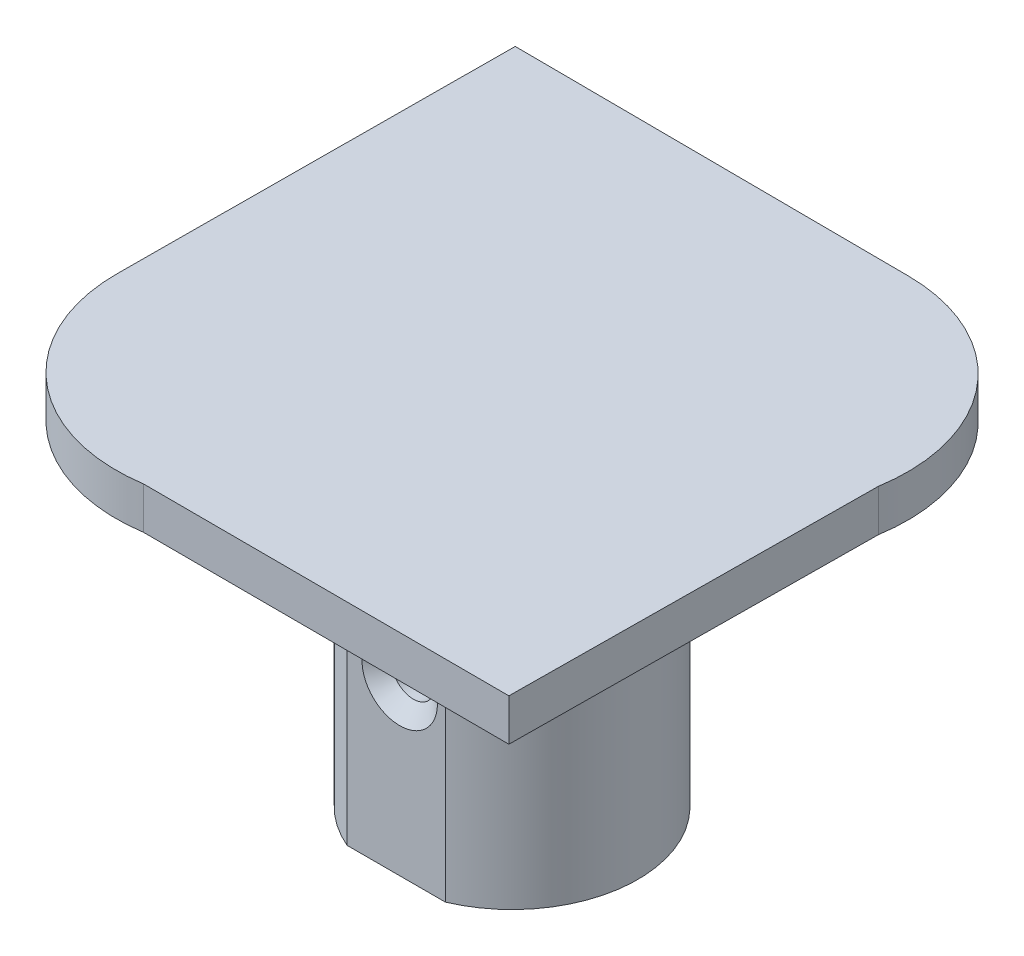
SolidWorks part; units mm, degrees
material "ABS"
ref_plane "Front Plane" through (0, 0, 0) normal (0, 0, 1) x (1, 0, 0)
ref_plane "Top Plane" through (0, 0, 0) normal (0, 1, 0) x (1, 0, 0)
ref_plane "Right Plane" through (0, 0, 0) normal (1, 0, 0) x (0, 0, -1)
sketch "Sketch2" plane through (0, 0, 0) normal (0, 1, 0) x (1, 0, 0)
  line L0 (2.8358, -0.2904) -> (10.2697, -0.2904)
  line L1 (2.8358, 17.2492) -> (10.2697, 17.2492)
  line L2 (6.5528, -0.2904) -> (6.5528, 17.2492) construction
  arc A0 (2.8358, 17.2492) -> (2.8358, -0.2904) centre (6.5528, 8.4794) ccw
  circle A1 centre (6.5528, 8.4794) radius 6.35
  arc A2 (10.2697, -0.2904) -> (10.2697, 17.2492) centre (6.5528, 8.4794) ccw
  dimension "D1" = 12.7
  dimension "D2" = 3.175
sketch "Sketch3" plane through (0, 0, 0) normal (0, 1, 0) x (1, 0, 0)
  line L0 (0, -12.8694) -> (27.7233, -12.933)
  line L1 (-14.7878, -0.0506) -> (-14.6178, 29.8917)
  line L4 (-14.6178, 29.8917) -> (27.7233, -12.933) construction
  line L5 (27.9746, 14.7893) -> (27.7233, -12.933)
  line L6 (15.3245, 29.7217) -> (-14.6178, 29.8917)
  arc A0 (-14.7878, -0.0506) -> (0, -12.8694) centre (-1.9188, -0.1438) ccw
  arc A2 (15.3245, 29.7217) -> (27.9746, 14.7893) centre (15.2716, 16.8524) cw
  point P8 (6.5528, 8.4794)
  dimension "D1" = 12.8694
extrude "Boss-Extrude1" add sketch "Sketch3" along normal blind 3.175 contours L4 L1 A0 L0 | L6 L4 L5 A2 | L0 L5 A2 L6 L1 A0 region at (-0.1371, 0, -1.8095) region at (13.2982, 0, -15.093)
ref_plane "Plane6" through (0, 0, 0) normal (0, -1, 0) x (-1, 0, 0)
sketch "Sketch11" plane through (0, 0, 0) normal (0, 1, 0) x (1, 0, 0)
  line L0 (20.07, -8.458) -> (21.4908, -8.4607)
  spline S0 degree 3 poles (22.9265, -1.3184) (22.9265, -4.6505) (22.9265, -7.9835) (22.9265, -11.3169) knots 3 3 3 3 4 4 4 4
  spline S1 degree 3 poles (12.9265, -1.3184) (16.2589, -1.3184) (19.5927, -1.3184) (22.9265, -1.3184) knots 2 2 2 2 3 3 3 3
  spline S2 degree 3 poles (12.9265, -11.3169) (12.9265, -7.9851) (12.9265, -4.6531) (12.9265, -1.3184) knots 1 1 1 1 2 2 2 2
  spline S3 degree 3 poles (22.9265, -11.3169) (19.5937, -11.3169) (16.2609, -11.3169) (12.9265, -11.3169) knots 0 0 0 0 1 1 1 1
  spline S4 degree 3 poles (15.7816, -4.1748) (17.1943, -4.1744) (20.0443, -4.1757) (20.0617, -4.1773) knots 0 0 0 0 1 1 1 1
  spline S5 degree 3 poles (20.0617, -4.1773) (20.0642, -4.1931) (20.0678, -7.048) (20.0673, -8.4607) knots 1 1 1 1 2 2 2 2
  spline S6 degree 2 poles (20.0673, -8.4607) (18.1734, -8.458) (17.2149, -8.458) knots 2 2 2 3 3 3
  spline S7 degree 3 poles (17.2149, -8.458) (17.2149, -8.9351) (17.2149, -9.4058) (17.2149, -9.8824) knots 3 3 3 3 4 4 4 4
  spline S8 degree 3 poles (17.2149, -9.8824) (16.7341, -9.8824) (16.2635, -9.8824) (15.7859, -9.8824) knots 4 4 4 4 5 5 5 5
  spline S9 degree 2 poles (15.7859, -9.8824) (15.7847, -9.8591) (15.7816, -4.1748) knots 5 5 5 6 6 6
  spline S10 degree 3 poles (15.7843, -4.1721) (15.3121, -4.1721) (14.8399, -4.1721) (14.3608, -4.1721) knots 0 0 0 0 1 1 1 1
  spline S11 degree 3 poles (14.3608, -4.1721) (14.3608, -3.6982) (14.3608, -3.2277) (14.3608, -2.7508) knots 1 1 1 1 2 2 2 2
  spline S12 degree 3 poles (14.3608, -2.7508) (14.8302, -2.7508) (15.3006, -2.7508) (15.7816, -2.7508) knots 2 2 2 2 3 3 3 3
  spline S13 degree 2 poles (15.7816, -2.7508) (15.7816, -3.2259) (15.7843, -4.1721) knots 3 3 3 4 4 4
  spline S15 degree 3 poles (20.07, -9.882) (20.07, -9.4069) (20.07, -8.9325) (20.07, -8.458) knots 2 2 2 2 3 3 3 3
  spline S16 degree 3 poles (21.4908, -9.882) (21.0214, -9.882) (20.551, -9.882) (20.07, -9.882) knots 1 1 1 1 2 2 2 2
  spline S17 degree 3 poles (21.4908, -8.4607) (21.4908, -8.9347) (21.4908, -9.4052) (21.4908, -9.882) knots 0 0 0 0 1 1 1 1
extrude "Cut-Extrude1" cut sketch "Sketch11" along normal blind 1.5
extrude "Boss-Extrude2" add sketch "Sketch2" against normal blind 25.4
sketch "Sketch14" plane through (0, 0, 0.2904) normal (0, 0, 1) x (1, 0, 0)
  line L0 (6.8149, -25.4) -> (6.8149, 0) construction
  line L1 (2.8358, -25.4) -> (10.2697, -25.4) construction
  line L2 (2.8358, 0) -> (10.2697, 0) construction
hole_wizard "CSK for #4 Flat Head Machine Screw (100)1" positions "Sketch15" profile "Sketch16" countersink size "#4" standard "ANSI Inch" end condition up to next
sketch "Sketch15" plane through (0, 0, 0.2904) normal (0, 0, 1) x (1, 0, 0)
  line L0 (6.8149, -25.4) -> (6.8149, 0) construction
  point P0 (6.8149, -12.7)
sketch "Sketch16" plane through (6.8149, -12.7, 0.2904) normal (1, 0, 0) x (0, -1, 0)
  line L0 (0, 0) -> (0, 2.4252)
  line L1 (0, 2.4252) -> (1.6319, 2.4252)
  line L2 (1.6319, 2.4252) -> (1.6319, 1.0284)
  line L3 (1.6319, 1.0284) -> (2.8575, 0)
  line L5 (2.8575, 0) -> (0, 0)
  line L6 (-1.6319, 1.0284) -> (-2.8575, 0) construction
  line L11 (0, -6.35) -> (0, 107.95) construction
  dimension "Thru Hole Dia." = 3.2639
  dimension "Thru Hole Depth" = 2.4252
  dimension "Near C'Sink Dia." = 5.715
  dimension "Near C'Sink Angle" = 100
fillet "Fillet1" radius 5 2 edges at (-2.9722, 0, -8.4794) (16.0778, 0, -8.4794)
